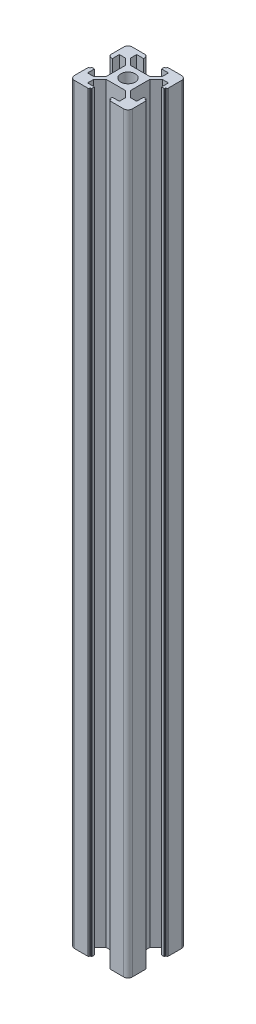
SolidWorks part; units mm, degrees
ref_plane "Front Plane" through (0, 0, 0) normal (0, 0, 1) x (1, 0, 0)
ref_plane "Top Plane" through (0, 0, 0) normal (0, 1, 0) x (1, 0, 0)
ref_plane "Right Plane" through (0, 0, 0) normal (1, 0, 0) x (0, 0, -1)
sketch "Sketch1" plane through (0, 0, 0) normal (0, 1, 0) x (1, 0, 0)
  line L0 (-8.5, 8.5) -> (8.5, 8.5)
  line L1 (-8.5, -10) -> (8.5, -10)
  line L2 (-10, -8.5) -> (-10, 8.5)
  line L3 (-8.5, 10) -> (8.5, 10)
  line L4 (10, -8.5) -> (10, 8.5)
  line L5 (-10, -10) -> (10, 10) construction
  line L6 (-10, 10) -> (10, -10) construction
  line L7 (8.5, -8.5) -> (8.5, 8.5)
  line L8 (-8.5, -8.5) -> (8.5, -8.5)
  line L9 (-8.5, -8.5) -> (-8.5, 8.5)
  line L10 (-10.4243, 9.5757) -> (9.5757, -10.4243)
  line L11 (-9.5757, -10.4243) -> (10.4243, 9.5757)
  line L12 (-9.5757, 10.4243) -> (10.4243, -9.5757)
  line L13 (-10.4243, -9.5757) -> (9.5757, 10.4243)
  line L14 (-9.5, -8.5) -> (-9.5, 8.5)
  line L15 (-10, -5.5) -> (10, -5.5)
  line L16 (-10, -5.5) -> (-10, 5.5)
  line L17 (-10, 5.5) -> (10, 5.5)
  line L18 (10, -5.5) -> (10, 5.5)
  line L19 (-10, -5.5) -> (10, 5.5) construction
  line L20 (-10, 5.5) -> (10, -5.5) construction
  line L21 (5.5, -10) -> (-5.5, -10)
  line L22 (5.5, -10) -> (5.5, 10)
  line L23 (5.5, 10) -> (-5.5, 10)
  line L24 (-5.5, -10) -> (-5.5, 10)
  line L25 (5.5, -10) -> (-5.5, 10) construction
  line L26 (5.5, 10) -> (-5.5, -10) construction
  line L27 (10, -3.1) -> (-10, -3.1)
  line L28 (10, -3.1) -> (10, 3.1)
  line L29 (10, 3.1) -> (-10, 3.1)
  line L30 (-10, -3.1) -> (-10, 3.1)
  line L31 (10, -3.1) -> (-10, 3.1) construction
  line L32 (10, 3.1) -> (-10, -3.1) construction
  line L33 (10, -3.6) -> (-10, -3.6)
  line L34 (10, -3.6) -> (10, 3.6)
  line L35 (10, 3.6) -> (-10, 3.6)
  line L36 (-10, -3.6) -> (-10, 3.6)
  line L37 (10, -3.6) -> (-10, 3.6) construction
  line L38 (10, 3.6) -> (-10, -3.6) construction
  line L39 (-8.5, 9.5) -> (8.5, 9.5)
  line L40 (9.5, -8.5) -> (9.5, 8.5)
  line L41 (-8.5, -9.5) -> (8.5, -9.5)
  arc A0 (-8.5, 10) -> (-10, 8.5) centre (-8.5, 8.5) ccw
  arc A1 (10, 8.5) -> (8.5, 10) centre (8.5, 8.5) ccw
  arc A2 (8.5, -10) -> (10, -8.5) centre (8.5, -8.5) ccw
  arc A3 (-10, -8.5) -> (-8.5, -10) centre (-8.5, -8.5) ccw
  arc A4 (8.5, 8.5) -> (8.5, 8.5) centre (8.5, 8.5) ccw
  arc A5 (8.5, -8.5) -> (8.5, -8.5) centre (8.5, -8.5) ccw
  arc A6 (-8.5, -8.5) -> (-8.5, -8.5) centre (-8.5, -8.5) ccw
  arc A7 (-8.5, 8.5) -> (-8.5, 8.5) centre (-8.5, 8.5) ccw
  circle A8 centre (0, 0) radius 2.5
  arc A9 (-8.5, 9.5) -> (-9.5, 8.5) centre (-8.5, 8.5) ccw
  arc A10 (9.5, 8.5) -> (8.5, 9.5) centre (8.5, 8.5) ccw
  arc A11 (8.5, -9.5) -> (9.5, -8.5) centre (8.5, -8.5) ccw
  arc A12 (-9.5, -8.5) -> (-8.5, -9.5) centre (-8.5, -8.5) ccw
  point P0 (0, 0)
  point P38 (0, 0)
  point P43 (0, 0)
  dimension "D3" = 1.5
  dimension "D4" = 1.5
  dimension "D5" = 1.5
  dimension "D6" = 1.5
  dimension "D12" = 5
  dimension "D1" = 20
  dimension "D2" = 20
  dimension "D10" = 11
  dimension "D11" = 11
  dimension "D13" = 6.2
  dimension "D14" = 7.2
  dimension "D7" = 1.5
  dimension "D8" = 0.6
  dimension "D9" = 0.6
  dimension "D15" = 0.5
sketch "Sketch2" plane through (0, 0, 0) normal (0, 1, 0) x (1, 0, 0)
  line L0 (-10, -8.5) -> (-10, 8.5) construction
  line L1 (-8.5, 10) -> (8.5, 10) construction
  line L2 (10, -8.5) -> (10, 8.5) construction
  line L3 (-8.5, -10) -> (8.5, -10) construction
  line L4 (-10, -8.5) -> (-10, 8.5)
  line L5 (-8.5, 10) -> (8.5, 10)
  line L6 (10, -8.5) -> (10, 8.5)
  line L7 (-8.5, -10) -> (8.5, -10)
  arc A0 (-8.5, 10) -> (-10, 8.5) centre (-8.5, 8.5) ccw construction
  arc A1 (10, 8.5) -> (8.5, 10) centre (8.5, 8.5) ccw construction
  arc A2 (8.5, -10) -> (10, -8.5) centre (8.5, -8.5) ccw construction
  arc A3 (-10, -8.5) -> (-8.5, -10) centre (-8.5, -8.5) ccw construction
  arc A4 (-8.5, 10) -> (-10, 8.5) centre (-8.5, 8.5) ccw
  arc A5 (10, 8.5) -> (8.5, 10) centre (8.5, 8.5) ccw
  arc A6 (8.5, -10) -> (10, -8.5) centre (8.5, -8.5) ccw
  arc A7 (-10, -8.5) -> (-8.5, -10) centre (-8.5, -8.5) ccw
extrude "Boss-Extrude1" add sketch "Sketch2" along normal blind 260
sketch "Sketch3" plane through (0, 260, 0) normal (0, 1, 0) x (1, 0, 0)
  line L3 (4.2, -4.2) -> (-4.2, -4.2)
  line L4 (4.2, -4.2) -> (4.2, 4.2)
  line L5 (4.2, 4.2) -> (-4.2, 4.2)
  line L6 (-4.2, -3.3515) -> (-4.2, 3.3515)
  line L7 (4.2, -4.2) -> (-4.2, 4.2) construction
  line L8 (4.2, 4.2) -> (-4.2, -4.2) construction
  line L10 (-10.4243, 9.5757) -> (9.5757, -10.4243) construction
  line L11 (-9.5757, 10.4243) -> (10.4243, -9.5757) construction
  line L12 (-10.4243, 9.5757) -> (-4.2, 3.3515)
  line L13 (-9.5757, 10.4243) -> (10.4243, -9.5757)
  line L15 (-8.5, -8.5) -> (-8.5, 8.5) construction
  line L16 (-8.5, -8.5) -> (-8.5, -3.1)
  line L17 (-10, 5.5) -> (10, 5.5) construction
  line L19 (10, -3.1) -> (-10, -3.1) construction
  line L20 (10, -3.6) -> (-10, -3.6) construction
  line L22 (10, 3.6) -> (-10, 3.6) construction
  line L23 (-10, -8.5) -> (-10, 8.5) construction
  line L24 (-10.4243, -9.5757) -> (9.5757, 10.4243) construction
  line L25 (-8.5, 5.5) -> (10, 5.5)
  line L26 (-10, -5.5) -> (10, -5.5) construction
  line L27 (10, -3.1) -> (-4.2, -3.1)
  line L28 (10, -3.6) -> (-4.4485, -3.6)
  line L29 (-10, -5.5) -> (10, -5.5)
  line L30 (10, 3.6) -> (-4.4485, 3.6)
  line L31 (-10, -8.5) -> (-10, -3.8)
  line L32 (-10.4243, -9.5757) -> (-4.2, -3.3515)
  line L33 (-10, 3.8) -> (-10, 8.5)
  line L34 (10, 3.1) -> (-10, 3.1) construction
  line L35 (10, 3.1) -> (-4.2, 3.1)
  line L36 (-9.5, -3.6) -> (-9.8, -3.6)
  line L37 (-8.5, -3.1) -> (-9.3, -3.1)
  line L38 (-9.5, 3.3) -> (-9.5, 3.6)
  line L39 (-8.5, 3.1) -> (-8.5, 8.5)
  line L40 (-9.5, 3.6) -> (-9.8, 3.6)
  line L41 (-9.5, -3.6) -> (-9.5, -3.3)
  line L42 (4.6515, -5.5) -> (10, -5.5)
  line L43 (-8.5, 3.1) -> (-9.3, 3.1)
  line L44 (-9.5, -8.5) -> (-9.5, 8.5) construction
  line L45 (-10, -8.5) -> (-10, 8.5)
  arc A0 (-9.8, -3.6) -> (-10, -3.8) centre (-9.8, -3.8) ccw
  arc A1 (-9.3, -3.1) -> (-9.5, -3.3) centre (-9.3, -3.3) ccw
  arc A2 (-9.5, 3.3) -> (-9.3, 3.1) centre (-9.3, 3.3) ccw
  arc A3 (-10, 3.8) -> (-9.8, 3.6) centre (-9.8, 3.8) ccw
  circle A6 centre (0, 0) radius 2.5 construction
  circle A7 centre (0, 0) radius 2.5
  point P0 (0, 0)
  point P55 (-9.5, 3.1)
  line M12 (-10, 8.5) -> (-10, -8.5)
  dimension "D2" = 0.2
  dimension "D3" = 0.2
  dimension "D4" = 0.2
  dimension "D5" = 0.2
  dimension "D7" = 4.3
extrude "Cut-Extrude1" cut sketch "Sketch3" against normal through all contours L39 L43 L38 L40 L36 L41 L37 L16 L29 L32 L6 L12 L25 M12 | L13 A7 | L13 A7 region at (-7.0241, 260, 0) region at (-0.5269, 260, 0.5269) region at (0.9842, 260, -0.9842)
ref_axis "Axis1" through (0, -20, 0) along (0, 1, 0)
pattern_circular "CirPattern1" count 4 over 360 about axis through (0, -20, 0) along (0, 1, 0) of "Cut-Extrude1"
sketch "Sketch4" plane through (0, 260, 0) normal (0, 1, 0) x (1, 0, 0)
sketch "Sketch5" plane through (0, 260, 0) normal (0, 1, 0) x (1, 0, 0)
  line L0 (-8.5, 3.1) -> (-9.3, 3.1) construction
  line L1 (-8.5, -3.1) -> (-9.3, -3.1) construction
  dimension "D1" = 6.2
